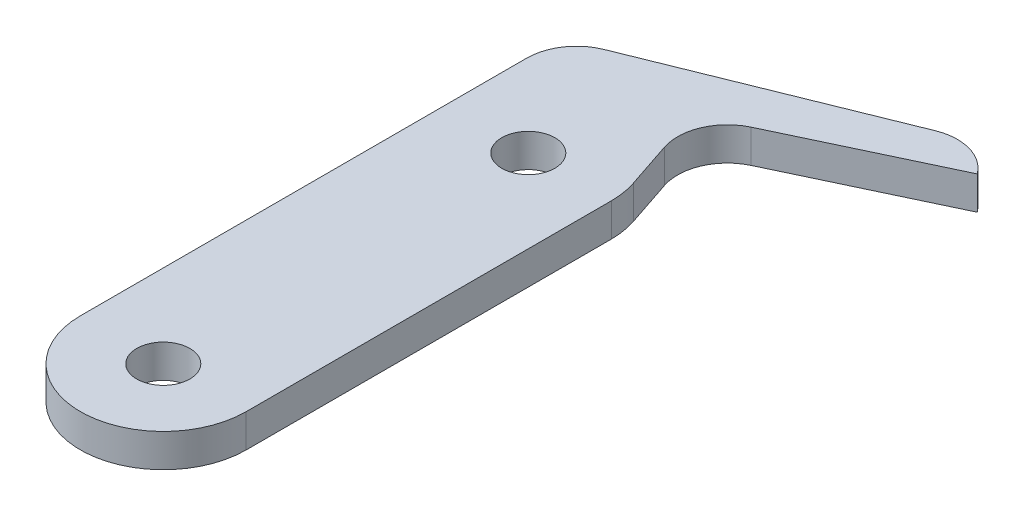
SolidWorks part; units mm, degrees
ref_plane "Front Plane" through (0, 0, 0) normal (0, 0, 1) x (1, 0, 0)
ref_plane "Top Plane" through (0, 0, 0) normal (0, 1, 0) x (1, 0, 0)
ref_plane "Right Plane" through (0, 0, 0) normal (1, 0, 0) x (0, 0, -1)
sketch "Sketch1" plane through (0, 0, 0) normal (0, 1, 0) x (1, 0, 0)
  line L5 (5, 11) -> (-5, 11)
  line L6 (5, 11) -> (5, -11)
  line L7 (5, -11) -> (-5, -11)
  line L8 (-5, 11) -> (-5, -11)
  line L9 (5, 11) -> (-5, -11) construction
  line L10 (5, -11) -> (-5, 11) construction
  circle A0 centre (0, 11) radius 1.6
  circle A1 centre (0, -11) radius 1.6
  circle A2 centre (0, 11) radius 5
  circle A7 centre (0, -11) radius 5
  point P0 (0, 0)
  point P1 (0, 0)
  dimension "D1" = 3.2
  dimension "D2" = 3.2
  dimension "D6" = 10
  dimension "D3" = 22
  dimension "D4" = 11
extrude "Boss-Extrude1" add sketch "Sketch1" along normal blind 1 and the other way blind 1 contours A2 | L7 A2 A0 | L7 A2 A0 | A1 | A1 region at (0, 0, -8.7133) region at (0, 0, -13.2867) region at (0, 0, 0) region at (0, 0, 13.2867) region at (0, 0, 8.7133)
sketch "Sketch4" plane through (0, 1, 0) normal (0, 1, 0) x (1, 0, 0)
  line L0 (-2.1353, 15.5211) -> (14.6235, 23.4361)
  line L1 (13.6664, 25.4626) -> (-5, 17.9268)
  line L2 (14.6235, 23.4361) -> (13.6664, 25.4626)
  line L3 (21.2032, -9.719) -> (8.8871, -14.6912) construction
  line L4 (-5, 17.9268) -> (-5, 8.1612)
  line L5 (-5, 11) -> (-5, -11) construction
  line L6 (2.9583, 17.9268) -> (4.7426, 12.5837)
  arc A0 (5, 11) -> (-5, 11) centre (0, 11) ccw construction
  circle A1 centre (0, 11) radius 5
  point P4 (0, 0)
  point P8 (1.8034, 17.4114)
  point P18 (0, 0)
  point P19 (2.9583, 17.9268)
  arc M6 (5, 11) -> (-5, 11) centre (0, 11) ccw
extrude "Boss-Extrude4" add sketch "Sketch4" against normal blind 2 contours L6 L0 M6 | L1 L4 L0 L2 M6 region at (3.6666, 1, -19.7644) region at (2.2055, 1, -16.164)
fillet "Fillet1" radius 3 3 edges at (2.9583, 0, -17.9268) (13.6664, 0, -25.4626) (-5, 0, -17.9268)
